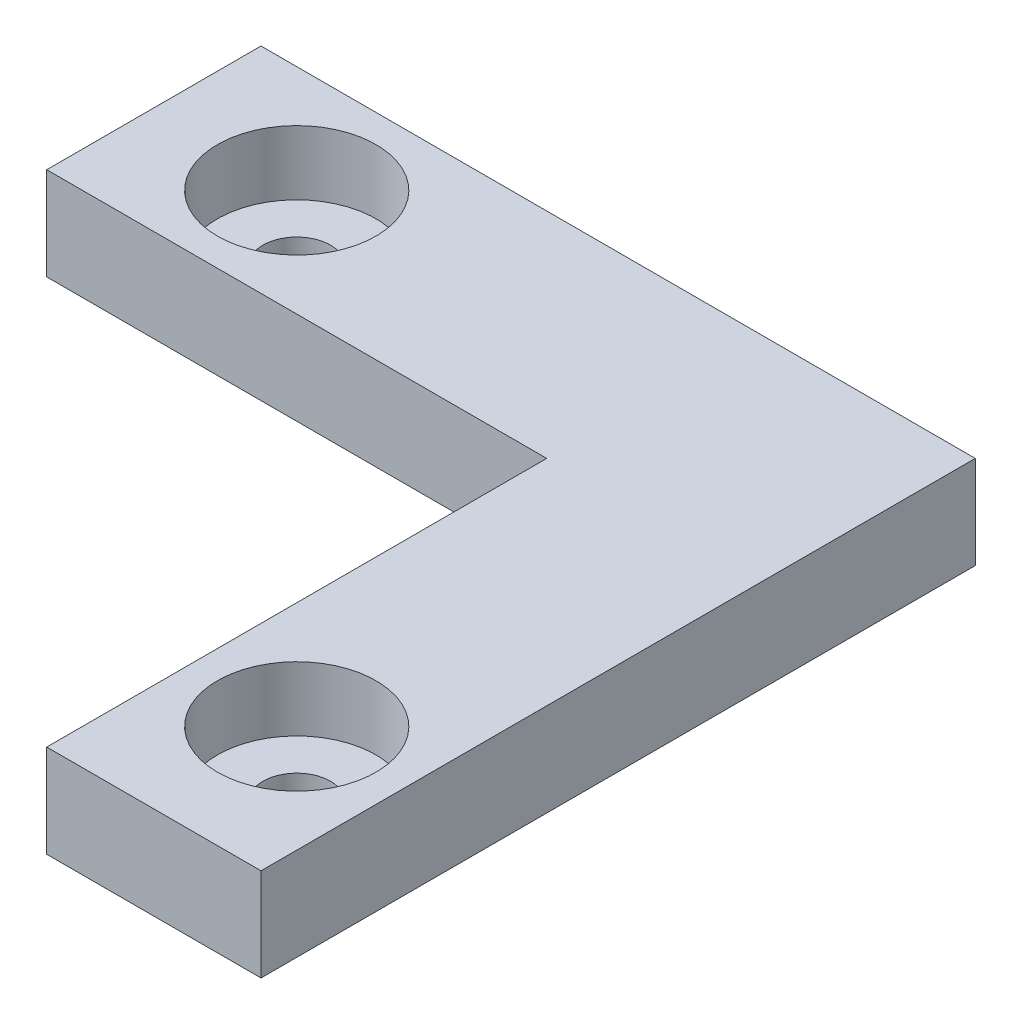
SolidWorks part; units mm, degrees
ref_plane "Front Plane" through (0, 0, 0) normal (0, 0, 1) x (1, 0, 0)
ref_plane "Top Plane" through (0, 0, 0) normal (0, 1, 0) x (1, 0, 0)
ref_plane "Right Plane" through (0, 0, 0) normal (1, 0, 0) x (0, 0, -1)
sketch "Sketch1" plane through (0, 0, 0) normal (0, 1, 0) x (1, 0, 0)
  line L0 (0, 9.525) -> (12.7, 9.525)
  line L2 (0, 0) -> (0, 19.05)
  line L3 (0, 19.05) -> (63.5, 19.05)
  line L4 (63.5, 0) -> (63.5, 19.05)
  line L5 (53.975, -44.45) -> (53.975, -31.75)
  line L7 (44.45, 0) -> (44.45, -44.45)
  line L8 (44.45, -44.45) -> (63.5, -44.45)
  line L9 (63.5, -44.45) -> (63.5, 0)
  line L10 (44.45, 0) -> (0, 0)
  circle A0 centre (12.7, 9.525) radius 3
  circle A2 centre (53.975, -31.75) radius 3
  circle A3 centre (53.975, -31.75) radius 7.05
  circle A4 centre (12.7, 9.525) radius 7.05
  dimension "D4" = 6
  dimension "D6" = 12.7
  dimension "D8" = 6
  dimension "D10" = 14.1
  dimension "D11" = 14.1
  dimension "D1" = 63.5
  dimension "D2" = 19.05
  dimension "D3" = 12.7
  dimension "D5" = 19.05
  dimension "D7" = 44.45
  dimension "D9" = 19.05
extrude "Boss-Extrude1" add sketch "Sketch1" along normal blind 8.255 contours L4 L3 L2 A0 region at (0.898, 0, -14.2875)
extrude "Boss-Extrude2" add sketch "Sketch1<3>" along normal blind 2.54 contours A4 A0 | A3 A2 region at (12.7, 0, -16.3756) region at (49.1309, 0, 26.9059)
sketch "Sketch1<3>" plane through (0, 0, 0) normal (0, 1, 0) x (1, 0, 0) same geometry as "Sketch1"
